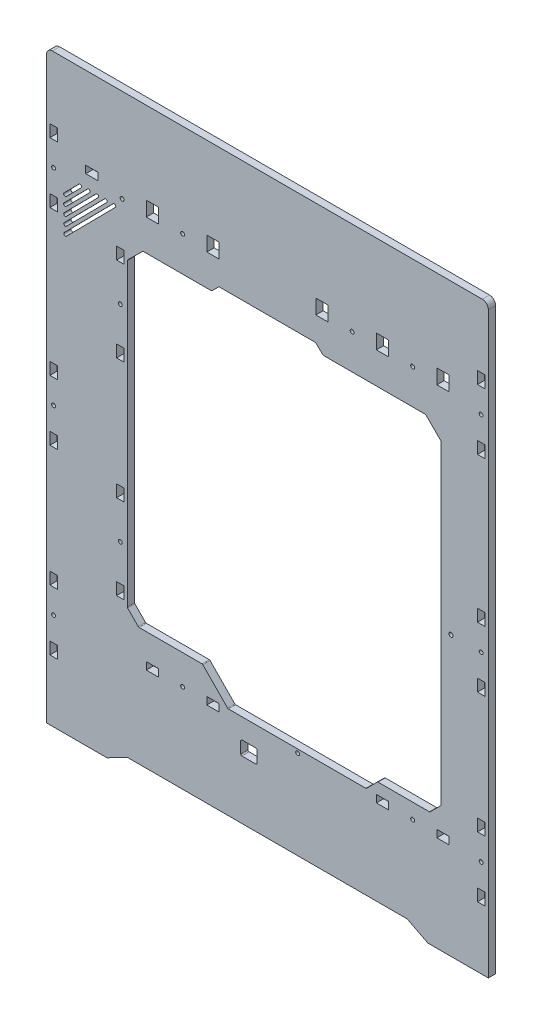
SolidWorks part; units mm, degrees
material "Клен"
ref_plane "Front" through (0, 0, 0) normal (0, 0, 1) x (1, 0, 0)
ref_plane "Top" through (0, 0, 0) normal (0, 1, 0) x (1, 0, 0)
ref_plane "Right" through (0, 0, 0) normal (1, 0, 0) x (0, 0, -1)
sketch "Эскиз1" plane through (0, 0, 0) normal (0, 0, 1) x (1, 0, 0)
  line L2 (738.4043, 525.0072) -> (1158.4308, 525.0072) construction
  line L3 (1133.3665, 477.0072) -> (1133.3665, 520.0072)
  line L4 (1128.3665, 525.0072) -> (773.3665, 525.0072)
  line L5 (768.3665, 520.0072) -> (768.3665, 477.0072)
  line L8 (1124.3665, 292.0072) -> (1130.4665, 292.0072)
  line L9 (1124.3665, 302.0072) -> (1124.3665, 292.0072)
  line L10 (1130.4665, 302.0072) -> (1124.3665, 302.0072)
  line L11 (1130.4665, 292.0072) -> (1130.4665, 302.0072)
  line L32 (1133.3665, 42.0072) -> (1133.3665, 477.0072)
  line L42 (768.3665, 477.0072) -> (768.3665, 42.0072)
  line L43 (768.3665, 42.0072) -> (818.3665, 42.0072)
  line L44 (818.3665, 42.0072) -> (835.3665, 50.7375)
  line L45 (835.3665, 50.7375) -> (1066.3665, 50.7375)
  line L46 (1066.3665, 50.7375) -> (1083.3665, 42.0072)
  line L47 (1083.3665, 42.0072) -> (1133.3665, 42.0072)
  line L48 (1124.3665, 242.0072) -> (1130.4665, 242.0072)
  line L49 (1124.3665, 252.0072) -> (1124.3665, 242.0072)
  line L50 (1130.4665, 252.0072) -> (1124.3665, 252.0072)
  line L51 (1130.4665, 242.0072) -> (1130.4665, 252.0072)
  line L56 (1124.3665, 142.0072) -> (1130.4665, 142.0072)
  line L57 (1124.3665, 152.0072) -> (1124.3665, 142.0072)
  line L58 (1130.4665, 152.0072) -> (1124.3665, 152.0072)
  line L59 (1130.4665, 142.0072) -> (1130.4665, 152.0072)
  line L64 (1124.3665, 92.0072) -> (1130.4665, 92.0072)
  line L65 (1124.3665, 102.0072) -> (1124.3665, 92.0072)
  line L66 (1130.4665, 102.0072) -> (1124.3665, 102.0072)
  line L67 (1130.4665, 92.0072) -> (1130.4665, 102.0072)
  line L72 (1100.8665, 127.1049) -> (1090.8665, 127.1049)
  line L73 (1100.8665, 121.0049) -> (1100.8665, 127.1049)
  line L74 (1090.8665, 121.0049) -> (1100.8665, 121.0049)
  line L75 (1090.8665, 127.1049) -> (1090.8665, 121.0049)
  line L80 (1050.8665, 127.1049) -> (1040.8665, 127.1049)
  line L81 (1050.8665, 121.0049) -> (1050.8665, 127.1049)
  line L82 (1040.8665, 121.0049) -> (1050.8665, 121.0049)
  line L83 (1040.8665, 127.1049) -> (1040.8665, 121.0049)
  line L88 (941.3665, 110.5049) -> (929.8665, 110.5049)
  line L89 (942.3665, 100.0049) -> (942.3665, 109.5049)
  line L90 (929.8665, 99.0049) -> (941.3665, 99.0049)
  line L91 (928.8665, 109.5049) -> (928.8665, 100.0049)
  line L96 (910.8665, 121.0049) -> (910.8665, 127.1049)
  line L97 (900.8665, 121.0049) -> (910.8665, 121.0049)
  line L98 (900.8665, 127.1049) -> (900.8665, 121.0049)
  line L99 (910.8665, 127.1049) -> (900.8665, 127.1049)
  line L104 (860.8665, 121.0049) -> (860.8665, 127.1049)
  line L105 (850.8665, 121.0049) -> (860.8665, 121.0049)
  line L106 (850.8665, 127.1049) -> (850.8665, 121.0049)
  line L107 (860.8665, 127.1049) -> (850.8665, 127.1049)
  line L112 (771.2665, 102.0072) -> (771.2665, 92.0072)
  line L113 (777.3665, 102.0072) -> (771.2665, 102.0072)
  line L114 (777.3665, 92.0072) -> (777.3665, 102.0072)
  line L115 (771.2665, 92.0072) -> (777.3665, 92.0072)
  line L120 (771.2665, 152.0072) -> (771.2665, 142.0072)
  line L121 (777.3665, 152.0072) -> (771.2665, 152.0072)
  line L122 (777.3665, 142.0072) -> (777.3665, 152.0072)
  line L123 (771.2665, 142.0072) -> (777.3665, 142.0072)
  line L128 (826.3665, 172.0072) -> (826.3665, 162.0072)
  line L129 (832.4665, 172.0072) -> (826.3665, 172.0072)
  line L130 (832.4665, 162.0072) -> (832.4665, 172.0072)
  line L131 (826.3665, 162.0072) -> (832.4665, 162.0072)
  line L136 (826.3665, 242.0072) -> (826.3665, 232.0072)
  line L137 (832.4665, 242.0072) -> (826.3665, 242.0072)
  line L138 (832.4665, 232.0072) -> (832.4665, 242.0072)
  line L139 (826.3665, 232.0072) -> (832.4665, 232.0072)
  line L144 (771.2665, 252.0072) -> (771.2665, 242.0072)
  line L145 (777.3665, 252.0072) -> (771.2665, 252.0072)
  line L146 (777.3665, 242.0072) -> (777.3665, 252.0072)
  line L147 (771.2665, 242.0072) -> (777.3665, 242.0072)
  line L152 (1124.3665, 412.0072) -> (1130.4665, 412.0072)
  line L153 (1124.3665, 422.0072) -> (1124.3665, 412.0072)
  line L154 (1130.4665, 422.0072) -> (1124.3665, 422.0072)
  line L155 (1130.4665, 412.0072) -> (1130.4665, 422.0072)
  line L160 (1124.3665, 462.0072) -> (1130.4665, 462.0072)
  line L161 (1124.3665, 472.0072) -> (1124.3665, 462.0072)
  line L162 (1130.4665, 472.0072) -> (1124.3665, 472.0072)
  line L163 (1130.4665, 462.0072) -> (1130.4665, 472.0072)
  line L168 (1090.8665, 457.1072) -> (1090.8665, 445.0072)
  line L169 (1100.8665, 457.1072) -> (1090.8665, 457.1072)
  line L170 (1100.8665, 445.0072) -> (1100.8665, 457.1072)
  line L171 (1090.8665, 445.0072) -> (1100.8665, 445.0072)
  line L176 (1040.8665, 457.1072) -> (1040.8665, 445.0072)
  line L177 (1050.8665, 457.1072) -> (1040.8665, 457.1072)
  line L178 (1050.8665, 445.0072) -> (1050.8665, 457.1072)
  line L179 (1040.8665, 445.0072) -> (1050.8665, 445.0072)
  line L184 (990.8665, 457.1072) -> (990.8665, 445.0072)
  line L185 (1000.8665, 457.1072) -> (990.8665, 457.1072)
  line L186 (1000.8665, 445.0072) -> (1000.8665, 457.1072)
  line L187 (990.8665, 445.0072) -> (1000.8665, 445.0072)
  line L192 (900.8665, 445.0072) -> (910.8665, 445.0072)
  line L193 (900.8665, 457.1072) -> (900.8665, 445.0072)
  line L194 (910.8665, 457.1072) -> (900.8665, 457.1072)
  line L195 (910.8665, 445.0072) -> (910.8665, 457.1072)
  line L200 (826.3665, 412.0072) -> (826.3665, 402.0072)
  line L201 (832.4665, 412.0072) -> (826.3665, 412.0072)
  line L202 (832.4665, 402.0072) -> (832.4665, 412.0072)
  line L203 (826.3665, 402.0072) -> (832.4665, 402.0072)
  line L224 (996.2808, 419.7551) -> (991.4523, 424.5835)
  line L225 (1081.1223, 419.1693) -> (997.695, 419.1693)
  line L226 (1094.1201, 406.6723) -> (1081.8269, 418.8789)
  line L227 (1094.4155, 146.42) -> (1094.4155, 405.9627)
  line L228 (1085.3572, 136.8536) -> (1094.1263, 145.7167)
  line L229 (1042.289, 136.5569) -> (1084.6463, 136.5569)
  line L230 (1032.8134, 127.4016) -> (1041.5781, 136.2603)
  line L231 (918.729, 127.1049) -> (1032.1025, 127.1049)
  line L232 (897.5745, 148.2016) -> (918.0158, 127.4039)
  line L233 (844.9385, 148.5006) -> (896.8613, 148.5006)
  line L234 (835.4584, 157.6604) -> (844.2276, 148.7973)
  line L235 (835.1693, 405.9627) -> (835.1693, 158.3637)
  line L236 (847.7579, 418.8789) -> (835.4647, 406.6723)
  line L237 (904.0381, 419.1693) -> (848.4625, 419.1693)
  line L238 (910.2808, 424.5835) -> (905.4523, 419.7551)
  line L239 (990.0381, 425.1693) -> (911.695, 425.1693)
  line L240 (850.8665, 445.0072) -> (860.8665, 445.0072)
  line L241 (850.8665, 457.1072) -> (850.8665, 445.0072)
  line L242 (860.8665, 457.1072) -> (850.8665, 457.1072)
  line L243 (860.8665, 445.0072) -> (860.8665, 457.1072)
  line L244 (784.8721, 398.2711) -> (825.3055, 439.1538)
  line L245 (823.528, 440.9118) -> (783.0946, 400.0291)
  line L248 (784.8331, 405.3421) -> (818.2346, 439.1147)
  line L249 (816.4571, 440.8727) -> (783.0556, 407.1001)
  line L252 (784.794, 412.4131) -> (811.1636, 439.0757)
  line L253 (809.3861, 440.8336) -> (783.0165, 414.171)
  line L256 (784.7549, 419.484) -> (804.0927, 439.0366)
  line L257 (802.3151, 440.7946) -> (782.9774, 421.242)
  line L260 (784.7159, 426.555) -> (797.0217, 438.9975)
  line L261 (795.2442, 440.7555) -> (782.9384, 428.313)
  line L268 (771.2665, 422.0072) -> (771.2665, 412.0072)
  line L269 (777.3665, 422.0072) -> (771.2665, 422.0072)
  line L270 (777.3665, 412.0072) -> (777.3665, 422.0072)
  line L271 (771.2665, 412.0072) -> (777.3665, 412.0072)
  line L276 (800.8665, 451.0072) -> (810.8665, 451.0072)
  line L277 (800.8665, 457.1072) -> (800.8665, 451.0072)
  line L278 (810.8665, 457.1072) -> (800.8665, 457.1072)
  line L279 (810.8665, 451.0072) -> (810.8665, 457.1072)
  line L284 (771.2665, 472.0072) -> (771.2665, 462.0072)
  line L285 (777.3665, 472.0072) -> (771.2665, 472.0072)
  line L286 (777.3665, 462.0072) -> (777.3665, 472.0072)
  line L287 (771.2665, 462.0072) -> (777.3665, 462.0072)
  line L292 (826.3665, 342.0072) -> (826.3665, 332.0072)
  line L293 (832.4665, 342.0072) -> (826.3665, 342.0072)
  line L294 (832.4665, 332.0072) -> (832.4665, 342.0072)
  line L295 (826.3665, 332.0072) -> (832.4665, 332.0072)
  line L300 (771.2665, 302.0072) -> (771.2665, 292.0072)
  line L301 (777.3665, 302.0072) -> (771.2665, 302.0072)
  line L302 (777.3665, 292.0072) -> (777.3665, 302.0072)
  line L303 (771.2665, 292.0072) -> (777.3665, 292.0072)
  arc A1 (1133.3665, 520.0072) -> (1128.3665, 525.0072) centre (1128.3665, 520.0072) ccw
  circle A2 centre (1127.4165, 272.0072) radius 1.6
  arc A3 (773.3665, 525.0072) -> (768.3665, 520.0072) centre (773.3665, 520.0072) ccw
  circle A4 centre (1102.521, 272.0072) radius 1.7
  circle A6 centre (1127.4165, 122.0072) radius 1.6
  circle A24 centre (1070.8665, 124.0549) radius 1.6
  circle A26 centre (975.8665, 124.0549) radius 1.6
  circle A28 centre (880.8665, 124.0549) radius 1.6
  arc A34 (929.8665, 110.5049) -> (928.8665, 109.5049) centre (929.8665, 109.5049) ccw
  arc A35 (942.3665, 109.5049) -> (941.3665, 110.5049) centre (941.3665, 109.5049) ccw
  arc A36 (941.3665, 99.0049) -> (942.3665, 100.0049) centre (941.3665, 100.0049) ccw
  arc A37 (928.8665, 100.0049) -> (929.8665, 99.0049) centre (929.8665, 100.0049) ccw
  circle A38 centre (774.3165, 122.0072) radius 1.6
  circle A40 centre (829.4165, 202.0072) radius 1.6
  circle A42 centre (774.3165, 272.0072) radius 1.6
  circle A44 centre (1127.4165, 442.0072) radius 1.6
  circle A46 centre (1070.8665, 448.0572) radius 1.6
  circle A48 centre (1020.8665, 448.0572) radius 1.6
  circle A50 centre (880.8665, 448.0572) radius 1.6
  circle A52 centre (830.8665, 448.0572) radius 1.6
  arc A56 (825.3055, 439.1538) -> (823.528, 440.9118) centre (824.4168, 440.0328) ccw
  arc A57 (783.0946, 400.0291) -> (784.8721, 398.2711) centre (783.9834, 399.1501) ccw
  arc A60 (818.2346, 439.1147) -> (816.4571, 440.8727) centre (817.3458, 439.9937) ccw
  arc A61 (783.0556, 407.1001) -> (784.8331, 405.3421) centre (783.9443, 406.2211) ccw
  arc A64 (811.1636, 439.0757) -> (809.3861, 440.8336) centre (810.2749, 439.9546) ccw
  arc A65 (783.0165, 414.171) -> (784.794, 412.4131) centre (783.9053, 413.292) ccw
  arc A82 (991.4523, 424.5835) -> (990.0381, 425.1693) centre (990.0381, 423.1693) ccw
  arc A83 (996.2808, 419.7551) -> (997.695, 419.1693) centre (997.695, 421.1693) ccw
  arc A84 (1081.8269, 418.8789) -> (1081.1223, 419.1693) centre (1081.1223, 418.1693) ccw
  arc A85 (1094.4155, 405.9627) -> (1094.1201, 406.6723) centre (1093.4155, 405.9627) ccw
  arc A86 (1094.1263, 145.7167) -> (1094.4155, 146.42) centre (1093.4155, 146.42) ccw
  arc A87 (1084.6463, 136.5569) -> (1085.3572, 136.8536) centre (1084.6463, 137.5569) ccw
  arc A88 (1042.289, 136.5569) -> (1041.5781, 136.2603) centre (1042.289, 135.5569) ccw
  arc A89 (1032.1025, 127.1049) -> (1032.8134, 127.4016) centre (1032.1025, 128.1049) ccw
  arc A90 (918.0158, 127.4039) -> (918.729, 127.1049) centre (918.729, 128.1049) ccw
  arc A91 (897.5745, 148.2016) -> (896.8613, 148.5006) centre (896.8613, 147.5006) ccw
  arc A92 (844.2276, 148.7973) -> (844.9385, 148.5006) centre (844.9385, 149.5006) ccw
  arc A93 (835.1693, 158.3637) -> (835.4584, 157.6604) centre (836.1693, 158.3637) ccw
  arc A94 (835.4647, 406.6723) -> (835.1693, 405.9627) centre (836.1693, 405.9627) ccw
  arc A95 (848.4625, 419.1693) -> (847.7579, 418.8789) centre (848.4625, 418.1693) ccw
  arc A96 (904.0381, 419.1693) -> (905.4523, 419.7551) centre (904.0381, 421.1693) ccw
  arc A97 (911.695, 425.1693) -> (910.2808, 424.5835) centre (911.695, 423.1693) ccw
  arc A100 (804.0927, 439.0366) -> (802.3151, 440.7946) centre (803.2039, 439.9156) ccw
  arc A101 (782.9774, 421.242) -> (784.7549, 419.484) centre (783.8662, 420.363) ccw
  arc A104 (797.0217, 438.9975) -> (795.2442, 440.7555) centre (796.1329, 439.8765) ccw
  arc A105 (782.9384, 428.313) -> (784.7159, 426.555) centre (783.8271, 427.434) ccw
  circle A106 centre (774.3165, 442.0072) radius 1.6
  circle A108 centre (829.4165, 372.0072) radius 1.6
  point P10 (1133.3665, 525.0072)
  point P14 (768.3665, 525.0072)
  dimension "D1" = 5
extrude "Бобышка-Вытянуть1" add sketch "Эскиз1" along normal blind 6 contours L42 L43 L44 L45 L46 L47 L32 L11 L8 L9 L10 L51 L48 L49 L50 L59 L56 L57 L58 L67 L64 L65 L66 L75 L72 L73 L74 L83 L80 L81 L82 L99 L96 L97 L98 region at (1127.3125, 259.5072, 0)
